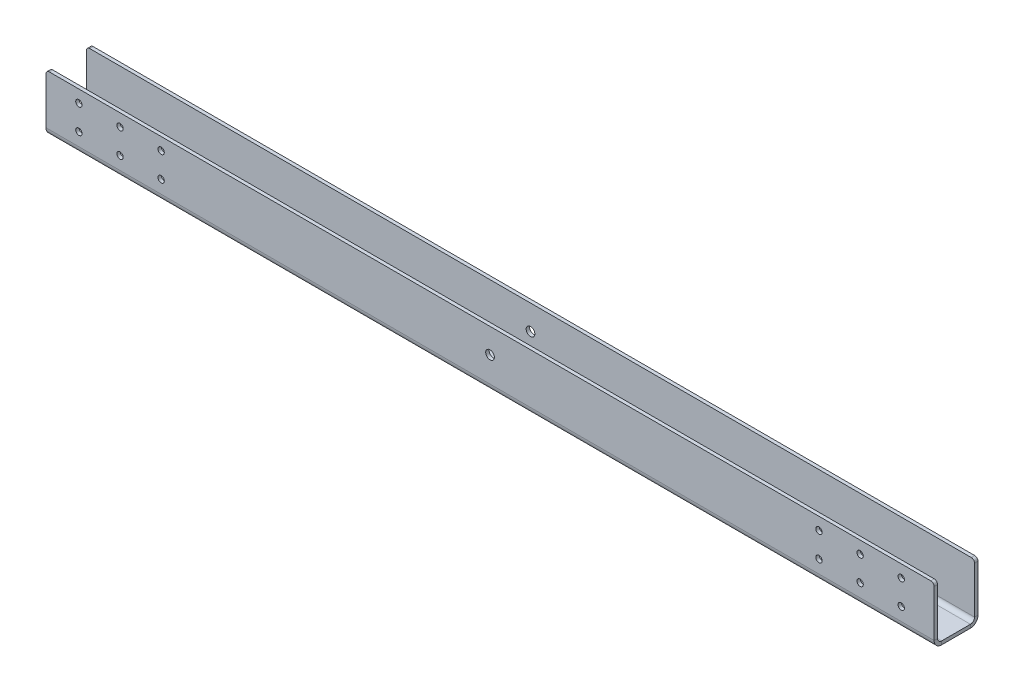
SolidWorks part; units mm, degrees
note: The reader was unsure of these and kept them because the rebuilt part matched: flange length of "Edge-Flange1", "Edge-Flange2".
material "Plain Carbon Steel"
ref_plane "Front Plane" through (0, 0, 0) normal (0, 0, 1) x (1, 0, 0)
ref_plane "Top Plane" through (0, 0, 0) normal (0, 1, 0) x (1, 0, 0)
ref_plane "Right Plane" through (0, 0, 0) normal (1, 0, 0) x (0, 0, -1)
sketch "Sketch1" plane through (0, 0, 0) normal (0, 1, 0) x (1, 0, 0)
  line L1 (0, 0) -> (685.8, 0)
  line L3 (0, 22.225) -> (685.8, 22.225)
  line L5 (26.924, 11.1125) -> (40.7341, 11.1125) construction
  line L12 (342.9, 0) -> (342.9, 76.0602) construction
  line L14 (658.876, 11.1125) -> (645.0659, 11.1125) construction
  line L21 (685.8, 0) -> (685.8, 22.225)
  line L22 (0, 0) -> (0, 22.225)
  dimension "D1" = 22.225
  dimension "D2" = 685.8
base flange "Base-Flange1" sketch "Sketch1" thickness 2.6568 reverse thickness direction no parameters "D1"=3.175
edge flange "Edge-Flange1" sketch "Sketch8" flange angle 90 flange length 44.45 flange position bend outside bend radius 3.175 thickness 2.6568 relief rectangular parameters "D6"=10
sketch "Sketch8" plane through (0, 0, 0) normal (0, 0, 1) x (1, 0, 0)
  line L2 (0, 0) -> (0, 41.7932)
  line L3 (0, 41.7932) -> (685.8, 41.7932)
  line L4 (685.8, 41.7932) -> (685.8, 0)
  line L7 (0, 0) -> (685.8, 0) construction
  line L8 (0, 0) -> (685.8, 0)
bend "EdgeBend1" bend radius 3.175 bend angle 90 parameters "D5"=1
edge flange "Edge-Flange2" sketch "Sketch11" flange angle 90 flange length 44.45 flange position bend outside bend radius 3.175 thickness 2.6568 relief rectangular parameters "D6"=10
sketch "Sketch11" plane through (0, 0, -22.225) normal (0, 0, -1) x (-1, 0, 0)
  line L2 (-685.8, 0) -> (-685.8, 41.7932)
  line L3 (-685.8, 41.7932) -> (0, 41.7932)
  line L4 (0, 41.7932) -> (0, 0)
  line L7 (-685.8, 0) -> (0, 0) construction
  line L8 (-685.8, 0) -> (0, 0)
bend "EdgeBend2" bend radius 3.175 bend angle 90 parameters "D5"=2
hole_wizard "17/64 (0.26563) Diameter Hole1" positions "Sketch26" profile "Sketch27" hole size "17/64" standard "ANSI Inch" end condition through all
sketch "Sketch26" plane through (0, 0, -28.0568) normal (0, 0, -1) x (-1, 0, 0)
  line L3 (-342.9, 3.175) -> (-342.9, 73.2705) construction
  line L4 (0, 3.175) -> (-685.8, 3.175) construction
  line L5 (-685.8, 41.7932) -> (0, 41.7932) construction
  point P2 (-342.9, 22.7432)
  dimension "D1" = 19.05
sketch "Sketch27" plane through (342.9, 22.7432, -28.0568) normal (1, 0, 0) x (0, 1, 0)
  line L0 (0, 0) -> (0, 33.8887)
  line L1 (0, 33.8887) -> (3.3735, 33.8887)
  line L2 (3.3735, 33.8887) -> (3.3735, 0)
  line L5 (3.3735, 0) -> (0, 0)
  line L11 (0, -6.35) -> (0, 107.95) construction
  dimension "Thru Hole Dia." = 6.747
  dimension "Thru Hole Depth" = 33.8887
hole_wizard "#10 (0.1935) Diameter Hole1" positions "Sketch28" profile "Sketch29" hole size "#10" standard "ANSI Inch" end condition up to next
sketch "Sketch28" plane through (0, 0, 5.8318) normal (0, 0, 1) x (1, 0, 0)
  point P0 (596.9, 13.2182)
  point P2 (596.9, 32.2682)
  point P4 (628.65, 32.2682)
  point P6 (628.65, 13.2182)
  point P8 (660.4, 13.2182)
  point P10 (660.4, 32.2682)
  point P12 (88.9, 13.2182)
  point P14 (88.9, 32.2682)
  point P16 (57.15, 13.2182)
  point P18 (57.15, 32.2682)
  point P20 (25.4, 13.2182)
  point P22 (25.4, 32.2682)
sketch "Sketch29" plane through (596.9, 13.2182, 5.8318) normal (1, 0, 0) x (0, -1, 0)
  line L0 (0, 0) -> (0, 2.6568)
  line L1 (0, 2.6568) -> (2.4574, 2.6568)
  line L2 (2.4574, 2.6568) -> (2.4574, 0)
  line L5 (2.4574, 0) -> (0, 0)
  line L11 (0, -6.35) -> (0, 107.95) construction
  dimension "Thru Hole Dia." = 4.9149
  dimension "Thru Hole Depth" = 2.6568
fillet "Fillet1" radius 2.54 4 edges at (685.8, 41.7932, 4.5034) (685.8, 41.7932, -26.7284) (0, 41.7932, -26.7284) (0, 41.7932, 4.5034)
sketch "Bend-Lines1" [suppressed] plane through (0, 0, 0) normal (0, 1, 0) x (1, 0, 0)
sketch "Bounding-Box1" [suppressed] plane through (0, 0, 0) normal (0, 1, 0) x (1, 0, 0)
sheet metal parameters "Sheet-Metal1" thickness 2.6568 parameters "D1"=3.175
flat pattern "Flat-Pattern1" [suppressed]
sketch "Bend-Lines2" plane through (0, 0, 0) normal (0, 1, 0) x (1, 0, 0)
sketch3d "Bounding-Box2" [suppressed]
  line L0 (717.55, 0, 0) -> (-44.45, 0, 0) construction
  line L1 (717.55, 44.45, 0) -> (-44.45, 44.45, 0) construction
  line L2 (717.55, 0, 0) -> (717.55, 44.45, 0) construction
  line L3 (-44.45, 0, 0) -> (-44.45, 44.45, 0) construction
sheet metal parameters "Sheet-Metal2" thickness 2.6568 parameters "D1"=3.175
flat pattern "Flat-Pattern1"
sketch "Bend-Lines2" plane through (0, 0, 0) normal (0, 1, 0) x (1, 0, 0)
  line L0 (0, -3.537) -> (673.1, -3.537) construction
  line L1 (0, -3.537) -> (673.1, -3.537) construction
sketch3d "Bounding-Box2" [suppressed]
  line L0 (717.55, -45.6921, 0) -> (-44.45, -45.6921, 0) construction
  line L1 (717.55, 44.45, 0) -> (-44.45, 44.45, 0) construction
  line L2 (717.55, -45.6921, 0) -> (717.55, 44.45, 0) construction
  line L3 (-44.45, -45.6921, 0) -> (-44.45, 44.45, 0) construction
bend of the flat pattern "Flatten-<EdgeBend1>1"
sheet metal parameters "Sheet-Metal3" thickness 2.6568 parameters "D1"=3.175
flat pattern "Flat-Pattern1"
sketch "Bend-Lines2" plane through (0, 0, 0) normal (0, 1, 0) x (1, 0, 0)
  line L0 (0, -3.537) -> (660.4, -3.537) construction
  line L1 (0, -3.537) -> (660.4, -3.537) construction
  line L2 (660.4, 35.287) -> (0, 35.287) construction
  line L3 (660.4, 35.287) -> (0, 35.287) construction
sketch3d "Bounding-Box2" [suppressed]
  line L0 (660.4, 77.4421, 0) -> (0, 77.4421, 0) construction
  line L1 (660.4, -45.6921, 0) -> (0, -45.6921, 0) construction
  line L2 (660.4, 77.4421, 0) -> (660.4, -45.6921, 0) construction
  line L3 (0, 77.4421, 0) -> (0, -45.6921, 0) construction
bend of the flat pattern "Flatten-<EdgeBend1>1"
bend of the flat pattern "Flatten-<EdgeBend2>1"
sheet metal parameters "Sheet-Metal8" thickness 2.6568 parameters "D1"=3.175
flat pattern "Flat-Pattern1"
sketch "Bend-Lines2" plane through (0, 0, 0) normal (0, 1, 0) x (1, 0, 0)
  line L0 (0, -3.537) -> (660.4, -3.537) construction
  line L1 (0, -3.537) -> (660.4, -3.537) construction
  line L2 (660.4, 28.937) -> (0, 28.937) construction
  line L3 (660.4, 28.937) -> (0, 28.937) construction
sketch3d "Bounding-Box2" [suppressed]
  line L0 (660.4, 71.0921, 0) -> (0, 71.0921, 0) construction
  line L1 (660.4, -45.6921, 0) -> (0, -45.6921, 0) construction
  line L2 (660.4, 71.0921, 0) -> (660.4, -45.6921, 0) construction
  line L3 (0, 71.0921, 0) -> (0, -45.6921, 0) construction
bend of the flat pattern "Flatten-<EdgeBend1>1"
bend of the flat pattern "Flatten-<EdgeBend2>1"
sheet metal parameters "Sheet-Metal10" thickness 2.6568 parameters "D1"=3.175
flat pattern "Flat-Pattern1"
sketch "Bend-Lines2" plane through (0, 0, 0) normal (0, 1, 0) x (1, 0, 0)
  line L0 (0, -3.537) -> (685.8, -3.537) construction
  line L1 (0, -3.537) -> (685.8, -3.537) construction
  line L2 (685.8, 25.762) -> (0, 25.762) construction
  line L3 (685.8, 25.762) -> (0, 25.762) construction
sketch3d "Bounding-Box2" [suppressed]
  line L0 (685.8, 67.9171, 0) -> (0, 67.9171, 0) construction
  line L1 (685.8, -45.6921, 0) -> (0, -45.6921, 0) construction
  line L2 (685.8, 67.9171, 0) -> (685.8, -45.6921, 0) construction
  line L3 (0, 67.9171, 0) -> (0, -45.6921, 0) construction
bend of the flat pattern "Flatten-<EdgeBend1>1"
bend of the flat pattern "Flatten-<EdgeBend2>1"
